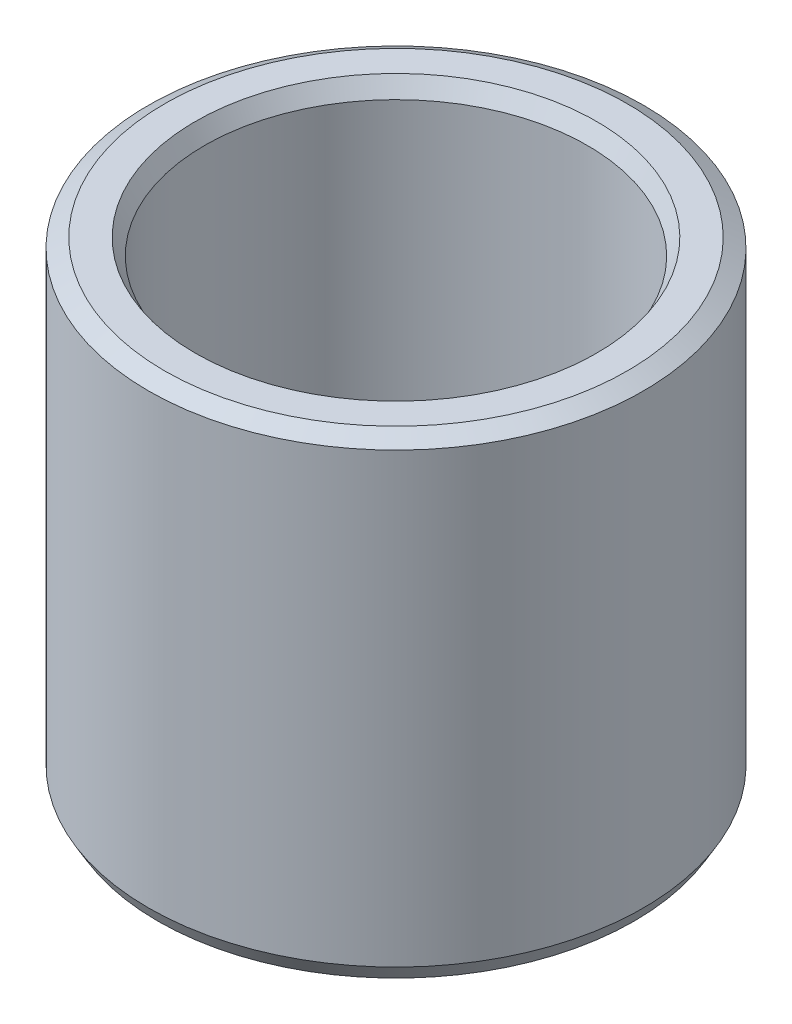
SolidWorks part; units mm, degrees
ref_plane "Front Plane" through (0, 0, 0) normal (0, 0, 1) x (1, 0, 0)
ref_plane "Top Plane" through (0, 0, 0) normal (0, 1, 0) x (1, 0, 0)
ref_plane "Right Plane" through (0, 0, 0) normal (1, 0, 0) x (0, 0, -1)
sketch "Sketch1" plane through (0, 0, 0) normal (0, 1, 0) x (1, 0, 0)
  circle A0 centre (0, 0) radius 35
  dimension "SLEEVE_OD" = 70
extrude "Boss-Extrude1" add sketch "Sketch1" along normal blind 66.9074
sketch "Sketch2" plane through (0, 0, 0) normal (0, 1, 0) x (1, 0, 0)
  circle A0 centre (0, 0) radius 27.0695
  dimension "BORE_D" = 54.1389
extrude "Cut-Extrude1" cut sketch "Sketch2" along normal through all
chamfer "Chamfer1" distance 1.3152 angle 60 4 edges at (0, 66.9074, 27.0695) (0, 0, 27.0695) (0, 0, 35) (0, 66.9074, 35) first distance on face at (0, 66.9074, 27.0695) first distance on face at (0, 0, 27.0695) first distance on face at (0, 66.9074, 35)
